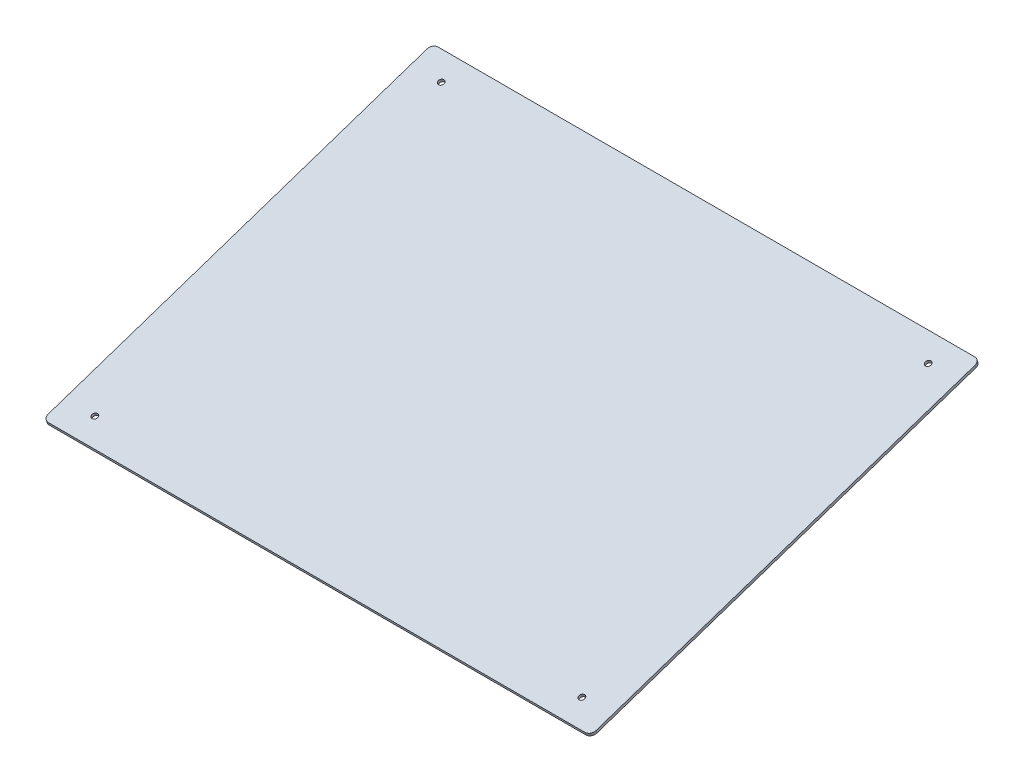
SolidWorks part; units mm, degrees
material "Acrylic (Medium-high impact)"
ref_plane "Front Plane" through (0, 0, 0) normal (0, 0, 1) x (1, 0, 0)
ref_plane "Top Plane" through (0, 0, 0) normal (0, 1, 0) x (1, 0, 0)
ref_plane "Right Plane" through (0, 0, 0) normal (1, 0, 0) x (0, 0, -1)
sketch "Sketch1" plane through (0, 0, 0) normal (1, 0, 0) x (0, 0, -1)
  line L0 (0, 0) -> (75.9126, 25.4)
  line L1 (75.9126, 25.4) -> (75.9126, 0) construction
  line L2 (75.9126, 0) -> (0, 0) construction
  dimension "D1" = 18.5
  dimension "D2" = 25.4
ref_plane "Display Plane" through (0, 0, 0) normal (0, -0.9483, -0.3173) x (0, 0.3173, -0.9483)
sketch "Sketch3" plane through (0, 0, 0) normal (0, -0.9483, -0.3173) x (0, 0.3173, -0.9483)
  line L0 (203.2, -270.9333) -> (203.2, 270.9333) construction
  line L1 (-228.6, 304.8) -> (228.6, 304.8)
  line L2 (-228.6, 304.8) -> (-228.6, -304.8)
  line L3 (-228.6, -304.8) -> (228.6, -304.8)
  line L4 (228.6, 304.8) -> (228.6, -304.8)
  line L5 (-228.6, 304.8) -> (228.6, -304.8) construction
  line L6 (-228.6, -304.8) -> (228.6, 304.8) construction
  line L7 (-203.2, -270.9333) -> (-203.2, 270.9333) construction
  line L8 (203.2, -270.9333) -> (-203.2, -270.9333) construction
  line L9 (203.2, 270.9333) -> (-203.2, 270.9333) construction
  line L10 (228.6, 0) -> (-228.6, 0) construction
  line L11 (0, -304.8) -> (0, 304.8) construction
  circle A1 centre (203.2, -270.9333) radius 3.175
  circle A5 centre (-203.2, -270.9333) radius 3.175
  circle A6 centre (-203.2, 270.9333) radius 3.175
  circle A7 centre (203.2, 270.9333) radius 3.175
  point P0 (0, 0)
  dimension "D5" = 6.35
  dimension "D6" = 6.35
  dimension "D1" = 609.6
  dimension "D2" = 457.2
  dimension "D3" = 25.4
  dimension "D4" = 25.4
extrude "Boss-Extrude1" add sketch "Sketch3" against normal blind 3.175
fillet "Fillet1" radius 6.35 4 edges at (-304.8, -71.0304, 217.2905) (-304.8, 74.0413, -216.2831) (304.8, 74.0413, -216.2831) (304.8, -71.0304, 217.2905)
ref_axis "Axis6" through (-270.9333, 69.2993, -191.0856) along (0, -0.9483, -0.3173)
ref_axis "Axis7" through (270.9333, 69.2993, -191.0856) along (0, -0.9483, -0.3173)
ref_axis "Axis8" through (-270.9333, -59.6534, 194.3131) along (0, -0.9483, -0.3173)
ref_axis "Axis9" through (270.9333, -59.6534, 194.3131) along (0, -0.9483, -0.3173)
equation "\"D6@Sketch3\"=\"D5@Sketch3\""
